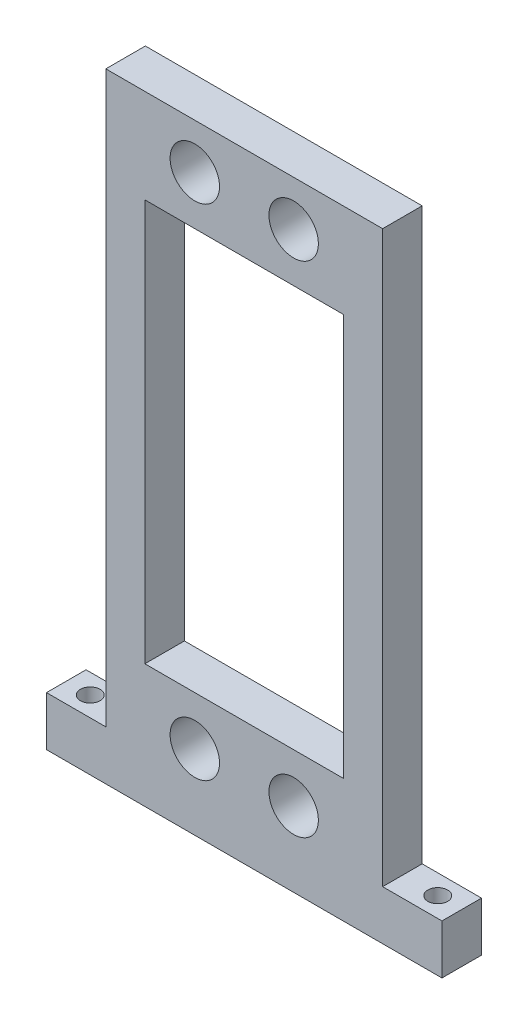
SolidWorks part; units mm, degrees
ref_plane "Front Plane" through (0, 0, 0) normal (0, 0, 1) x (1, 0, 0)
ref_plane "Top Plane" through (0, 0, 0) normal (0, 1, 0) x (1, 0, 0)
ref_plane "Right Plane" through (0, 0, 0) normal (1, 0, 0) x (0, 0, -1)
sketch "Sketch1" plane through (0, 0, 0) normal (0, 0, 1) x (1, 0, 0)
  line L0 (0, 5) -> (6, 5)
  line L2 (6, 5) -> (6, 62.64)
  line L4 (34, 5) -> (34, 62.64)
  line L5 (0, 0) -> (40, 0)
  line L6 (0, 0) -> (0, 5)
  line L8 (40, 0) -> (40, 5)
  line L9 (34, 5) -> (40, 5)
  line L10 (6, 62.64) -> (34, 62.64)
  dimension "D1" = 57.64
  dimension "D3" = 40
  dimension "D2" = 28
  dimension "D4" = 5
extrude "Boss-Extrude1" add sketch "Sketch1" along normal blind 4
sketch "Sketch2" plane through (0, 0, 4) normal (0, 0, 1) x (1, 0, 0)
  line L0 (15, 58.07) -> (25, 58.07) construction
  line L1 (15, 7.57) -> (25, 7.57) construction
  line L3 (34, 62.64) -> (6, 62.64) construction
  line L4 (40, 5) -> (34, 5) construction
  circle A0 centre (15, 7.57) radius 2.5
  circle A1 centre (25, 7.57) radius 2.5
  circle A2 centre (15, 58.07) radius 2.5
  circle A3 centre (25, 58.07) radius 2.5
  point P11 (20, 7.57)
  point P21 (20, 62.64)
  dimension "D2" = 5
  dimension "D1" = 2.57
  dimension "D3" = 10
  dimension "D4" = 4.57
extrude "Cut-Extrude1" cut sketch "Sketch2" against normal through all
sketch "Sketch3" plane through (0, 5, 0) normal (0, 1, 0) x (1, 0, 0)
  line L0 (2.4249, -2) -> (37.5751, -2) construction
  line L1 (34, -4) -> (6, -4) construction
  line L2 (40, -4) -> (40, 0) construction
  circle A0 centre (2.4249, -2) radius 1
  circle A1 centre (37.5751, -2) radius 1
  point P2 (20, -2)
  point P7 (20, -4)
  point P11 (40, -2)
  dimension "D1" = 2
extrude "Cut-Extrude2" cut sketch "Sketch3" against normal blind 10
sketch "Sketch4" plane through (0, 0, 4) normal (0, 0, 1) x (1, 0, 0)
  line L11 (30.05, 53.14) -> (9.95, 53.14)
  line L12 (30.05, 53.14) -> (30.05, 12.5)
  line L13 (30.05, 12.5) -> (9.95, 12.5)
  line L14 (9.95, 53.14) -> (9.95, 12.5)
  line L16 (34, 62.64) -> (6, 62.64) construction
  circle A0 centre (25, 58.07) radius 2.5 construction
  circle A1 centre (25, 58.07) radius 2.5 construction
  point P6 (20, 12.5)
  point P12 (20, 62.64)
  dimension "D1" = 4.93
  dimension "D5" = 20.1
  dimension "D6" = 40.64
extrude "Cut-Extrude6" cut sketch "Sketch4" against normal blind 10
